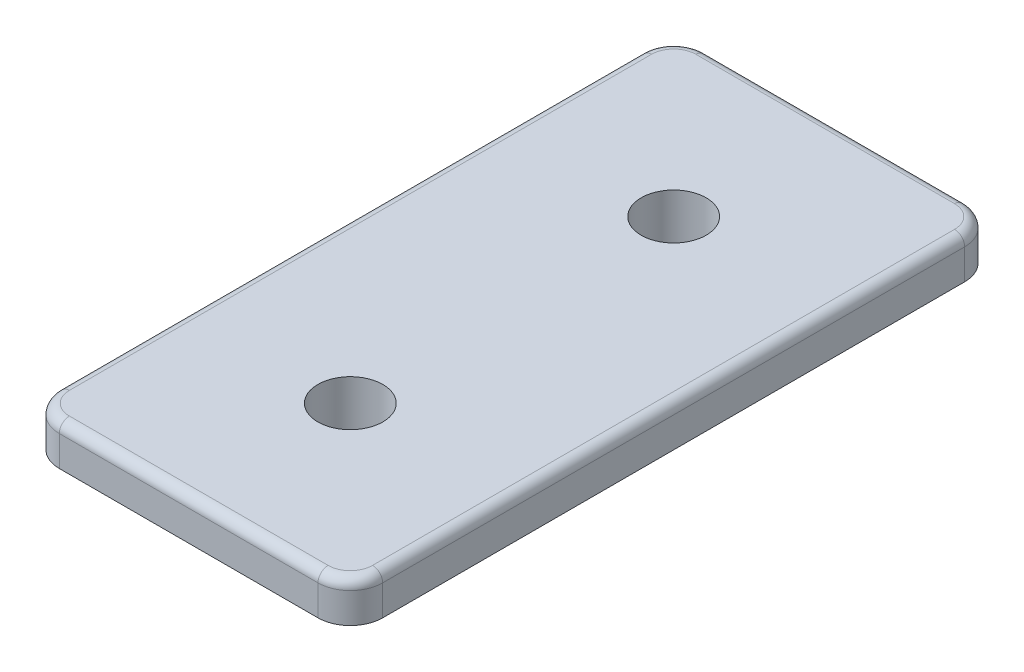
SolidWorks part; units mm, degrees
ref_plane "Front Plane" through (0, 0, 0) normal (0, 0, 1) x (1, 0, 0)
ref_plane "Top Plane" through (0, 0, 0) normal (0, 1, 0) x (1, 0, 0)
ref_plane "Right Plane" through (0, 0, 0) normal (1, 0, 0) x (0, 0, -1)
sketch "Sketch1" plane through (0, 0, 0) normal (0, 1, 0) x (1, 0, 0)
  line L0 (-11.1125, 23.8125) -> (11.1125, 23.8125)
  line L1 (-12.7, -25.4) -> (12.7, -25.4)
  line L2 (-12.7, -25.4) -> (-12.7, 25.4)
  line L3 (-12.7, 25.4) -> (12.7, 25.4)
  line L4 (12.7, -25.4) -> (12.7, 25.4)
  line L5 (-12.7, -25.4) -> (12.7, 25.4) construction
  line L6 (-12.7, 25.4) -> (12.7, -25.4) construction
  line L7 (11.1125, -23.8125) -> (11.1125, 23.8125)
  line L8 (-11.1125, -23.8125) -> (11.1125, -23.8125)
  line L9 (-11.1125, -23.8125) -> (-11.1125, 23.8125)
  line L10 (-10.8585, 23.5585) -> (10.8585, 23.5585)
  line L11 (10.8585, -23.5585) -> (10.8585, 23.5585)
  line L12 (-10.8585, -23.5585) -> (10.8585, -23.5585)
  line L13 (-10.8585, -23.5585) -> (-10.8585, 23.5585)
  point P0 (0, 0)
  dimension "D1" = 50.8
  dimension "D2" = 25.4
  dimension "D3" = 1.5875
  dimension "D4" = 0.254
extrude "Boss-Extrude1" add sketch "Sketch1" along normal blind 0.762 contours L13 L12 L11 L10 region at (0, 0, 0)
sketch "Sketch2" plane through (0, 0.762, 0) normal (0, 1, 0) x (1, 0, 0)
  line L1 (-12.7, -25.4) -> (12.7, -25.4)
  line L2 (-12.7, -25.4) -> (-12.7, 25.4)
  line L3 (-12.7, 25.4) -> (12.7, 25.4)
  line L4 (12.7, -25.4) -> (12.7, 25.4)
  line L5 (-12.7, -25.4) -> (12.7, 25.4) construction
  line L6 (-12.7, 25.4) -> (12.7, -25.4) construction
  point P0 (0, 0)
  dimension "D1" = 25.4
  dimension "D2" = 50.8
extrude "Boss-Extrude2" add sketch "Sketch2" along normal blind 3.175
sketch "Sketch3" plane through (0, 3.937, 0) normal (0, 1, 0) x (1, 0, 0)
  line L0 (-12.7, 25.4) -> (-12.7, -25.4) construction
  line L1 (-12.7, 0) -> (12.7, 0) construction
  line L2 (12.7, -25.4) -> (12.7, 25.4) construction
  circle A0 centre (0, 12.7) radius 2.5527
  circle A1 centre (0, -12.7) radius 2.5527
  dimension "D1" = 5.1054
  dimension "D2" = 12.7
  dimension "D3" = 12.7
extrude "Cut-Extrude1" cut sketch "Sketch3" against normal through all
fillet "Fillet1" radius 2.54 8 edges at (-10.8585, 0.381, 23.5585) (10.8585, 0.381, 23.5585) (-10.8585, 0.381, -23.5585) (10.8585, 0.381, -23.5585) (12.7, 2.3495, -25.4) (12.7, 2.3495, 25.4) (-12.7, 2.3495, -25.4) (-12.7, 2.3495, 25.4)
fillet "Fillet3" radius 0.7937 8 edges at (-11.9561, 3.937, -24.6561) (0, 3.937, -25.4) (11.9561, 3.937, -24.6561) (12.7, 3.937, 0) (11.9561, 3.937, 24.6561) (0, 3.937, 25.4) (-11.9561, 3.937, 24.6561) (-12.7, 3.937, 0)
